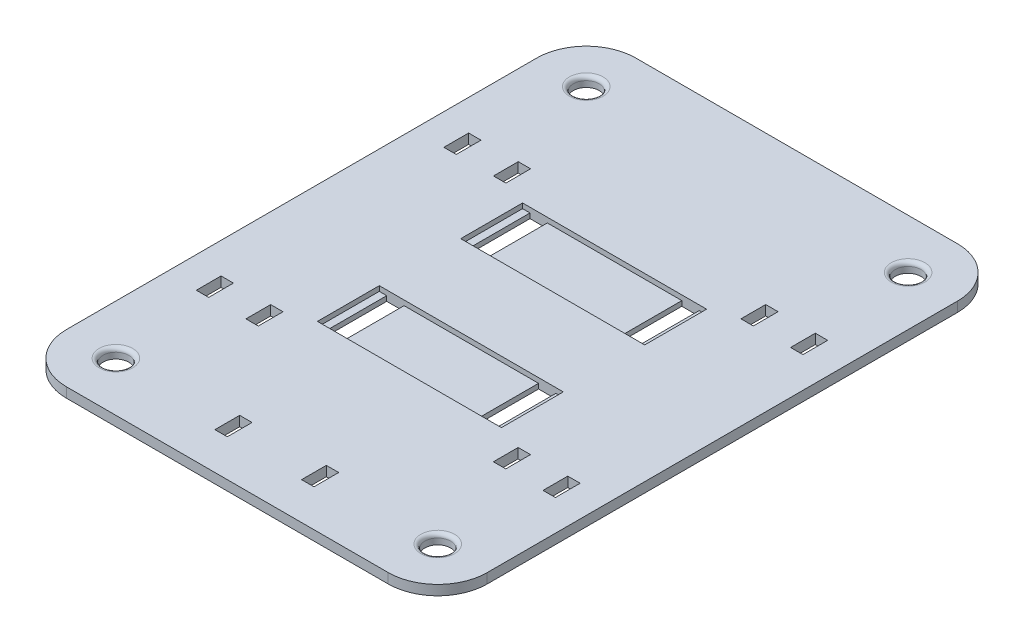
SolidWorks part; units mm, degrees
material "3-D Printed ABS"
ref_plane "Front Plane" through (0, 0, 0) normal (0, 0, 1) x (1, 0, 0)
ref_plane "Top Plane" through (0, 0, 0) normal (0, 1, 0) x (1, 0, 0)
ref_plane "Right Plane" through (0, 0, 0) normal (1, 0, 0) x (0, 0, -1)
sketch "Sketch1" plane through (0, 0, 0) normal (0, 1, 0) x (1, 0, 0)
  line L1 (-53.975, -73.025) -> (53.975, -73.025)
  line L2 (-53.975, -73.025) -> (-53.975, 73.025)
  line L3 (-53.975, 73.025) -> (53.975, 73.025)
  line L4 (53.975, -73.025) -> (53.975, 73.025)
  line L5 (-53.975, -73.025) -> (53.975, 73.025) construction
  line L6 (-53.975, 73.025) -> (53.975, -73.025) construction
  point P0 (0, 0)
  dimension "D1" = 107.95
  dimension "PlateY" = 146.05
extrude "Boss-Extrude1" add sketch "Sketch1" against normal blind 2.54
sketch "Sketch2" plane through (0, 0, 0) normal (0, 1, 0) x (1, 0, 0)
  line L0 (0, 0) -> (100.1618, 0) construction
  line L1 (0, 0) -> (0, 86.3534) construction
  line L2 (-53.975, 73.025) -> (-53.975, -73.025) construction
  line L3 (53.975, 73.025) -> (-53.975, 73.025) construction
  line L4 (0, 0) -> (-53.975, 73.025) construction
  circle A0 centre (-41.275, 60.325) radius 3.302
  circle A1 centre (41.275, 60.325) radius 3.302
  circle A2 centre (41.275, -60.325) radius 3.302
  circle A3 centre (-41.275, -60.325) radius 3.302
  dimension "D1" = 6.604
  dimension "D3" = 12.7
  dimension "D2" = 12.7
extrude "Cut-Extrude1" cut sketch "Sketch2" against normal through all
sketch "Sketch3" plane through (0, 0, 0) normal (0, 1, 0) x (1, 0, 0)
  line L0 (-53.975, 0) -> (53.975, 0) construction
  line L1 (-21.695, 26.3125) -> (-17.25, 26.3125)
  line L2 (-21.695, 26.3125) -> (-21.695, 10.4375)
  line L3 (-21.695, 10.4375) -> (-17.25, 10.4375)
  line L4 (-17.25, 26.3125) -> (-17.25, 10.4375)
  line L5 (17.25, 26.3125) -> (17.25, 10.4375)
  line L6 (21.695, 10.4375) -> (17.25, 10.4375)
  line L7 (21.695, 26.3125) -> (21.695, 10.4375)
  line L8 (21.695, 26.3125) -> (17.25, 26.3125)
  line L9 (-53.975, 73.025) -> (-53.975, -73.025) construction
  line L10 (53.975, -73.025) -> (53.975, 73.025) construction
  line L11 (0, -18.375) -> (0, 79.6704) construction
  line L12 (0, 18.375) -> (0, -79.6704) construction
  line L13 (21.695, -26.3125) -> (17.25, -26.3125)
  line L14 (21.695, -26.3125) -> (21.695, -10.4375)
  line L15 (21.695, -10.4375) -> (17.25, -10.4375)
  line L16 (17.25, -26.3125) -> (17.25, -10.4375)
  line L17 (-17.25, -26.3125) -> (-17.25, -10.4375)
  line L18 (-21.695, -10.4375) -> (-17.25, -10.4375)
  line L19 (-21.695, -26.3125) -> (-21.695, -10.4375)
  line L20 (-21.695, -26.3125) -> (-17.25, -26.3125)
  line L21 (-21.695, 18.375) -> (-33.6921, 18.375) construction
  line L22 (-53.975, -73.025) -> (53.975, -73.025) construction
  point P31 (0, -73.025)
  point P32 (-53.975, 0)
  dimension "D1" = 15.875
  dimension "D2" = 4.445
  dimension "D3" = 17.25
  dimension "D4" = 18.375
  dimension "D5" = 18.375
extrude "Cut-Extrude2" cut sketch "Sketch3" against normal through all
fillet "Fillet1" radius 12.7 4 edges at (53.975, -1.27, -73.025) (53.975, -1.27, 73.025) (-53.975, -1.27, 73.025) (-53.975, -1.27, -73.025)
sketch "Sketch4" plane through (0, 0, 0) normal (0, 1, 0) x (1, 0, 0)
  line L0 (0, 0) -> (80.9727, -80.9727) construction
  line L1 (0, 0) -> (-80.9727, -80.9727) construction
  line L2 (69.1118, -51.1513) -> (28.7006, -10.7401)
  line L3 (28.7006, -10.7401) -> (10.7401, -28.7006)
  line L4 (10.7401, -28.7006) -> (51.1513, -69.1118)
  line L5 (51.1513, -69.1118) -> (69.1118, -51.1513)
  line L6 (0, 0) -> (0, -118.7381) construction
  line L7 (0, 0) -> (-98.4177, 0) construction
  line L8 (-51.1513, -69.1118) -> (-69.1118, -51.1513)
  line L9 (-69.1118, -51.1513) -> (-28.7006, -10.7401)
  line L10 (-28.7006, -10.7401) -> (-10.7401, -28.7006)
  line L11 (-10.7401, -28.7006) -> (-51.1513, -69.1118)
  line L12 (-69.1118, 51.1513) -> (-28.7006, 10.7401)
  line L13 (-51.1513, 69.1118) -> (-69.1118, 51.1513)
  line L14 (-10.7401, 28.7006) -> (-51.1513, 69.1118)
  line L15 (-28.7006, 10.7401) -> (-10.7401, 28.7006)
  line L16 (51.1513, 69.1118) -> (69.1118, 51.1513)
  line L17 (69.1118, 51.1513) -> (28.7006, 10.7401)
  line L18 (28.7006, 10.7401) -> (10.7401, 28.7006)
  line L19 (10.7401, 28.7006) -> (51.1513, 69.1118)
  point P6 (19.7204, -19.7204)
  dimension "D1" = 25.4
  dimension "D2" = 57.15
  dimension "D3" = 45
extrude "Cut-Extrude3" [suppressed] cut sketch "Sketch4" against normal blind 1.5875
sketch "Sketch6" [suppressed] plane through (0, 0, 0) normal (0, 1, 0) x (1, 0, 0)
  line L0 (46.3377, -44.1074) -> (34.6634, -32.4331) construction
  line L1 (0, 0) -> (0, -117.7376) construction
  line L2 (0, 0) -> (-151.7285, 0) construction
  line L4 (28.1601, -10.1996) -> (10.1996, -28.1601) construction
  line L5 (50.6107, -68.5712) -> (68.5712, -50.6107) construction
  text T0 "ESC" font "Century Gothic" height in points 22
  dimension "D1" = 45
  dimension "D2" = 20.32
  dimension "D3" = 20.32
extrude "Cut-Extrude5" [suppressed] cut sketch "Sketch6" against normal blind 3.175
sketch "Sketch5" plane through (0, 0, 0) normal (0, 1, 0) x (1, 0, 0)
  line L0 (41.275, 73.025) -> (-41.275, 73.025) construction
  line L1 (14.2875, 15.875) -> (-14.2875, 15.875)
  line L2 (14.2875, 15.875) -> (14.2875, 66.675)
  line L3 (14.2875, 66.675) -> (-14.2875, 66.675)
  line L4 (-14.2875, 15.875) -> (-14.2875, 66.675)
  point P4 (0, 15.875)
  dimension "D1" = 50.8
  dimension "D2" = 28.575
  dimension "D3" = 6.35
extrude "Cut-Extrude4" [suppressed] cut sketch "Sketch5" against normal blind 1.5875
ref_axis "Axis1" through (0, 0.3175, 0) along (0, -1, 0)
pattern_circular "CirPattern1" [suppressed] count 4 over 360 about axis through (0, 0.3175, 0) along (0, -1, 0) of bodies 105
sketch "Sketch7" plane through (0, 0, 0) normal (0, 1, 0) x (1, 0, 0)
  line L0 (0, 0) -> (0, -54.962) construction
  line L1 (63.4018, -13.3522) -> (38.0018, -13.3522)
  line L2 (63.4018, -13.3522) -> (63.4018, 43.7978)
  line L3 (63.4018, 43.7978) -> (38.0018, 43.7978)
  line L4 (38.0018, -13.3522) -> (38.0018, 43.7978)
  line L5 (-38.0018, -13.3522) -> (-38.0018, 43.7978)
  line L6 (-63.4018, 43.7978) -> (-38.0018, 43.7978)
  line L7 (-63.4018, -13.3522) -> (-63.4018, 43.7978)
  line L8 (-63.4018, -13.3522) -> (-38.0018, -13.3522)
  line L9 (-41.275, -73.025) -> (41.275, -73.025) construction
  line L10 (38.5677, -40.64) -> (-18.5823, -40.64)
  line L11 (38.5677, -40.64) -> (38.5677, -66.04)
  line L12 (38.5677, -66.04) -> (-18.5823, -66.04)
  line L13 (-18.5823, -40.64) -> (-18.5823, -66.04)
  line L14 (38.5677, -40.64) -> (-18.5823, -66.04) construction
  line L15 (38.5677, -66.04) -> (-18.5823, -40.64) construction
  line L16 (19.844, -36.1003) -> (-37.306, -36.1003)
  line L17 (19.844, -36.1003) -> (19.844, -61.5003)
  line L18 (19.844, -61.5003) -> (-37.306, -61.5003)
  line L19 (-37.306, -36.1003) -> (-37.306, -61.5003)
  line L20 (19.844, -36.1003) -> (-37.306, -61.5003) construction
  line L21 (19.844, -61.5003) -> (-37.306, -36.1003) construction
  point P11 (9.9927, -53.34)
  point P18 (-8.731, -48.8003)
  dimension "D1" = 57.15
  dimension "D2" = 25.4
  dimension "D3" = 57.15
  dimension "D4" = 25.4
  dimension "D5" = 6.985
  dimension "D6" = 57.15
  dimension "D7" = 25.4
extrude "Cut-Extrude6" [suppressed] cut sketch "Sketch7" against normal blind 1.27
sketch "Sketch8" plane through (0, 0, 0) normal (0, 1, 0) x (1, 0, 0)
  line L7 (19.05, -31.75) -> (-19.05, -31.75)
  line L8 (19.05, -31.75) -> (19.05, 31.75)
  line L9 (19.05, 31.75) -> (-19.05, 31.75)
  line L10 (-19.05, -31.75) -> (-19.05, 31.75)
  point P0 (0, 0)
  dimension "D1" = 38.1
  dimension "D2" = 31.75
  dimension "D3" = 63.5
extrude "Boss-Extrude3" [suppressed] add sketch "Sketch8" along normal blind 2.54
sketch "Sketch11" plane through (0, 0, 0) normal (0, 1, 0) x (1, 0, 0)
  line L0 (-21.695, -26.3125) -> (-17.25, -26.3125) construction
  line L1 (23.6, -26.3125) -> (-23.6, -26.3125)
  line L2 (23.6, -26.3125) -> (23.6, -10.4375)
  line L3 (23.6, -10.4375) -> (-23.6, -10.4375)
  line L4 (-23.6, -26.3125) -> (-23.6, -10.4375)
  line L5 (21.695, -10.4375) -> (17.25, -10.4375) construction
  line L6 (21.695, -26.3125) -> (21.695, -10.4375) construction
  line L7 (-21.695, -10.4375) -> (-21.695, -26.3125) construction
  line L8 (0, 0) -> (90.9737, 0) construction
  line L9 (-23.6, 26.3125) -> (-23.6, 10.4375)
  line L10 (23.6, 10.4375) -> (-23.6, 10.4375)
  line L11 (23.6, 26.3125) -> (23.6, 10.4375)
  line L12 (23.6, 26.3125) -> (-23.6, 26.3125)
  dimension "D1" = 1.905
  dimension "D2" = 1.905
extrude "Cut-Extrude9" cut sketch "Sketch11" against normal mid plane 2.54
sketch "Sketch12" plane through (0, 0, 0) normal (0, 1, 0) x (1, 0, 0)
  line L1 (12.7, -34.5105) -> (-12.7, -34.5105)
  line L2 (12.7, -34.5105) -> (12.7, -18.375)
  line L3 (12.7, -18.375) -> (-12.7, -18.375)
  line L4 (-12.7, -34.5105) -> (-12.7, -18.375)
  line L6 (23.8125, 0) -> (-23.8125, 0) construction
  line L7 (-53.975, 60.325) -> (-53.975, -60.325) construction
  line L9 (-12.7, 34.5105) -> (-12.7, 18.375)
  line L10 (12.7, 18.375) -> (-12.7, 18.375)
  line L11 (12.7, 34.5105) -> (12.7, 18.375)
  line L12 (12.7, 34.5105) -> (-12.7, 34.5105)
  point P6 (-53.975, 0)
  dimension "D1" = 25.4
  dimension "D2" = 18.375
extrude "Cut-Extrude12" [suppressed] cut sketch "Sketch12" along normal through all
sketch "Sketch9" plane through (0, 0, 0) normal (0, 1, 0) x (1, 0, 0)
  line L1 (25.1579, -52.4084) -> (-25.6421, -52.4084)
  line L2 (25.1579, -52.4084) -> (25.1579, -1.6084)
  line L3 (25.1579, -1.6084) -> (-25.6421, -1.6084)
  line L4 (-25.6421, -52.4084) -> (-25.6421, -1.6084)
  line L5 (25.1579, -52.4084) -> (-25.6421, -1.6084) construction
  line L6 (25.1579, -1.6084) -> (-25.6421, -52.4084) construction
  point P0 (-0.2421, -27.0084)
  dimension "D1" = 50.8
  dimension "D2" = 50.8
sketch "Sketch13" plane through (0, 0, 0) normal (0, 1, 0) x (1, 0, 0)
  line L0 (0, 0) -> (0, -106.7514) construction
  line L1 (34.925, 3.175) -> (28.575, 3.175)
  line L2 (34.925, 3.175) -> (34.925, -3.175)
  line L3 (34.925, -3.175) -> (28.575, -3.175)
  line L4 (28.575, 3.175) -> (28.575, -3.175)
  line L5 (34.925, 3.175) -> (28.575, -3.175) construction
  line L6 (34.925, -3.175) -> (28.575, 3.175) construction
  line L7 (-34.925, -3.175) -> (-28.575, 3.175) construction
  line L8 (-34.925, 3.175) -> (-28.575, -3.175) construction
  line L9 (-28.575, 3.175) -> (-28.575, -3.175)
  line L10 (-34.925, -3.175) -> (-28.575, -3.175)
  line L11 (-34.925, 3.175) -> (-34.925, -3.175)
  line L12 (-34.925, 3.175) -> (-28.575, 3.175)
  point P0 (31.75, 0)
  point P12 (-31.75, 0)
  dimension "D1" = 6.35
  dimension "D2" = 28.575
  dimension "D3" = 0
extrude "Cut-Extrude13" [suppressed] cut sketch "Sketch13" against normal through all
fillet "Fillet2" radius 1.016 4 edges at (41.275, 0, -63.627) (-41.275, 0, -57.023) (-41.275, 0, 57.023) (41.275, 0, 63.627)
sketch "Sketch14" plane through (0, 0, 0) normal (0, 1, 0) x (1, 0, 0)
  line L0 (0, 76.698) -> (0, -76.698) construction
  line L1 (33.3248, -34.925) -> (30.1498, -34.925)
  line L2 (33.3248, -34.925) -> (33.3248, -28.575)
  line L3 (33.3248, -28.575) -> (30.1498, -28.575)
  line L4 (30.1498, -34.925) -> (30.1498, -28.575)
  line L5 (0, 0) -> (-92.4571, 0) construction
  line L6 (-30.1498, -34.925) -> (-30.1498, -28.575)
  line L7 (-33.3248, -28.575) -> (-30.1498, -28.575)
  line L8 (-33.3248, -34.925) -> (-33.3248, -28.575)
  line L9 (-33.3248, -34.925) -> (-30.1498, -34.925)
  line L10 (-33.3248, 34.925) -> (-30.1498, 34.925)
  line L11 (-33.3248, 34.925) -> (-33.3248, 28.575)
  line L12 (-33.3248, 28.575) -> (-30.1498, 28.575)
  line L13 (-30.1498, 34.925) -> (-30.1498, 28.575)
  line L14 (30.1498, 34.925) -> (30.1498, 28.575)
  line L15 (33.3248, 28.575) -> (30.1498, 28.575)
  line L16 (33.3248, 34.925) -> (33.3248, 28.575)
  line L17 (33.3248, 34.925) -> (30.1498, 34.925)
  line L18 (-41.275, -73.025) -> (41.275, -73.025) construction
  line L19 (-9.525, -63.5) -> (-9.525, -57.15)
  line L20 (12.7, -63.5) -> (9.525, -63.5)
  line L21 (12.7, -63.5) -> (12.7, -57.15)
  line L22 (12.7, -57.15) -> (9.525, -57.15)
  line L23 (38.1, -73.025) -> (38.1, 73.025) construction
  line L24 (41.275, 73.025) -> (-41.275, 73.025) construction
  line L25 (42.8752, 34.925) -> (46.0502, 34.925)
  line L26 (42.8752, 34.925) -> (42.8752, 28.575)
  line L27 (42.8752, 28.575) -> (46.0502, 28.575)
  line L28 (46.0502, 34.925) -> (46.0502, 28.575)
  line L29 (46.0502, -34.925) -> (46.0502, -28.575)
  line L30 (42.8752, -28.575) -> (46.0502, -28.575)
  line L31 (42.8752, -34.925) -> (42.8752, -28.575)
  line L32 (42.8752, -34.925) -> (46.0502, -34.925)
  line L33 (-46.0502, 34.925) -> (-46.0502, 28.575)
  line L34 (-42.8752, 28.575) -> (-46.0502, 28.575)
  line L35 (-42.8752, 34.925) -> (-42.8752, 28.575)
  line L36 (-42.8752, 34.925) -> (-46.0502, 34.925)
  line L37 (-42.8752, -34.925) -> (-46.0502, -34.925)
  line L38 (-42.8752, -34.925) -> (-42.8752, -28.575)
  line L39 (-42.8752, -28.575) -> (-46.0502, -28.575)
  line L40 (-46.0502, -34.925) -> (-46.0502, -28.575)
  line L41 (53.975, -50.8) -> (-53.975, -50.8) construction
  line L42 (53.975, -60.325) -> (53.975, 60.325) construction
  line L43 (-53.975, 60.325) -> (-53.975, -60.325) construction
  line L44 (0, -178.298) -> (0, -24.902) construction
  line L45 (9.525, -63.5) -> (9.525, -57.15)
  line L46 (-12.7, -57.15) -> (-9.525, -57.15)
  line L47 (-12.7, -63.5) -> (-12.7, -57.15)
  line L48 (-12.7, -63.5) -> (-9.525, -63.5)
  dimension "D2" = 3.175
  dimension "D3" = 6.35
  dimension "D4" = 28.575
  dimension "D5" = 3.175
  dimension "D6" = 6.35
  dimension "D7" = 9.525
  dimension "D8" = 9.525
  dimension "D9" = 38.1
  dimension "D10" = 22.225
  dimension "D11" = 30.1498
extrude "Cut-Extrude14" cut sketch "Sketch14" against normal through all
equation "\"Plate Dim Y\"= \"Plate Dim Y@Quad Assemb.SLDASM\""
equation "\"PlateY@Sketch1\" = \"Plate Dim Y\""
equation "\"D1@Sketch1\"= \"Plate Dim X\""
equation "\"D1@Boss-Extrude1\" = \"Plate Thickness\""
equation "\"Plate Dim X\"= \"Plate Dim X@Quad Assemb.SLDASM\""
equation "\"Plate Thickness\"= \"Plate Thickness@Quad Assemb.sldasm\""
equation "\"Batt X\"= \"Batt X@Quad Assemb.sldasm\""
equation "\"Batt Y\"= \"Batt Y@Quad Assemb.sldasm\""
equation "\"D3@Sketch3\"=\"Batt X\"/2"
equation "\"D4@Sketch3\"=\"Batt Y\"/4"
equation "\"D5@Sketch3\"=\"Batt Y\"*2/8"
equation "\"Dowell Width\"= \"Dowell Width@Quad Assemb.sldasm\""
equation "\"D1@Sketch2\"=\"Dowell Width\"+.01"
equation "\"D2@Sketch12\"=\"Batt Y\"/4"
